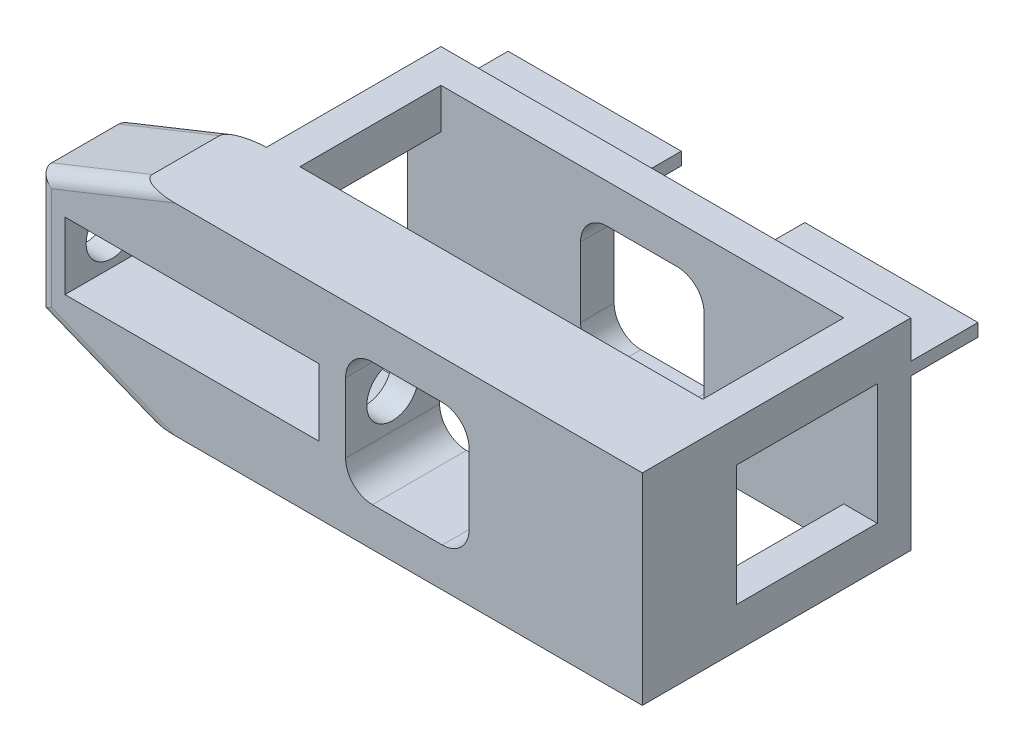
SolidWorks part; units mm, degrees
other "Markup1"
sketch "Sketch12" plane through (0, 38.1, 0) normal (-0.0705, 0.1614, 0.9844) x (0.9933, -0.0793, 0.0841)
material "ABS"
ref_plane "Front Plane" through (0, 0, 0) normal (0, 0, 1) x (1, 0, 0)
ref_plane "Top Plane" through (0, 0, 0) normal (0, 1, 0) x (1, 0, 0)
ref_plane "Right Plane" through (0, 0, 0) normal (1, 0, 0) x (0, 0, -1)
sketch "Sketch1" plane through (0, 0, 0) normal (0, 0, 1) x (1, 0, 0)
  line L1 (0, 0) -> (88.9, 0)
  line L2 (0, 0) -> (0, 38.1)
  line L3 (0, 38.1) -> (88.9, 38.1)
  line L4 (88.9, 0) -> (88.9, 38.1)
  line L5 (0, 0) -> (-25.4, 0)
  line L6 (0, 0) -> (0, 38.1)
  line L7 (0, 38.1) -> (-25.4, 38.1)
  line L8 (-25.4, 0) -> (-25.4, 38.1)
  dimension "D1" = 88.9
  dimension "D2" = 38.1
extrude "Boss-Extrude1" add sketch "Sketch1" against normal blind 17.78 contours L1 L4 L3 L2 | L8 L5 L2 L7 region at (44.45, 19.05, 0) region at (-12.7, 19.05, 0)
sketch "Sketch2" plane through (0, 0, 0) normal (0, 0, 1) x (1, 0, 0)
  line L0 (0, 19.05) -> (88.9, 19.05) construction
  line L1 (0, 0) -> (0, 38.1) construction
  line L2 (88.9, 0) -> (88.9, 38.1) construction
  line L3 (44.45, 0) -> (44.45, 38.1) construction
  line L4 (0, 0) -> (88.9, 0) construction
  line L5 (0, 38.1) -> (88.9, 38.1) construction
  line L6 (88.9, 30.48) -> (82.55, 30.48)
  line L7 (37.846, 30.734) -> (51.054, 30.734)
  line L8 (32.766, 25.654) -> (32.766, 12.446)
  line L9 (37.846, 7.366) -> (51.054, 7.366)
  line L10 (56.134, 25.654) -> (56.134, 12.446)
  line L11 (0, 38.1) -> (6.35, 38.1)
  line L12 (0, 38.1) -> (0, 30.48)
  line L13 (0, 30.48) -> (6.35, 30.48)
  line L14 (6.35, 38.1) -> (6.35, 30.48)
  line L15 (82.55, 38.1) -> (82.55, 30.48)
  line L16 (88.9, 38.1) -> (82.55, 38.1)
  line L17 (88.9, 38.1) -> (88.9, 30.48)
  line L18 (88.9, 0) -> (88.9, 7.62)
  line L19 (88.9, 0) -> (82.55, 0)
  line L20 (82.55, 0) -> (82.55, 7.62)
  line L21 (88.9, 7.62) -> (82.55, 7.62)
  line L22 (0, 7.62) -> (6.35, 7.62)
  line L23 (6.35, 0) -> (6.35, 7.62)
  line L24 (0, 0) -> (6.35, 0)
  line L25 (0, 0) -> (0, 7.62)
  line L26 (-25.4, 0) -> (-25.4, 38.1) construction
  line L27 (27.686, 25.4) -> (-10.414, 25.4)
  line L28 (27.686, 25.4) -> (27.686, 12.7)
  line L29 (27.686, 12.7) -> (-10.414, 12.7)
  line L30 (-10.414, 25.4) -> (-10.414, 12.7)
  line L31 (-25.4, 38.1) -> (88.9, 38.1) construction
  line L32 (-10.414, 25.4) -> (-20.32, 25.4)
  line L33 (-10.414, 25.4) -> (-10.414, 12.7)
  line L34 (-10.414, 12.7) -> (-20.32, 12.7)
  line L35 (-20.32, 25.4) -> (-20.32, 12.7)
  arc A0 (32.766, 12.446) -> (37.846, 7.366) centre (37.846, 12.446) ccw
  arc A1 (51.054, 7.366) -> (56.134, 12.446) centre (51.054, 12.446) ccw
  arc A2 (51.054, 30.734) -> (56.134, 25.654) centre (51.054, 25.654) cw
  arc A3 (37.846, 30.734) -> (32.766, 25.654) centre (37.846, 25.654) ccw
  point P47 (56.134, 7.366)
  point P50 (56.134, 30.734)
  point P53 (32.766, 30.734)
  dimension "D12" = 5.08
  dimension "D1" = 23.368
  dimension "D3" = 32.766
  dimension "D7" = 6.35
  dimension "D10" = 12.7
  dimension "D2" = 23.368
  dimension "D4" = 11.684
  dimension "D11" = 6.35
  dimension "D8" = 5.08
  dimension "D9" = 38.1
  dimension "D5" = 7.62
  dimension "D6" = 5.08
extrude "Cut-Extrude1" cut sketch "Sketch2" against normal blind 41.402 contours L27 L30 L29 L28 | L14 L11 L12 L13 | L25 L24 L23 L22 | L10 L7 L8 L9 | L17 L16 L15 L6 | L18 L21 L20 L19 | L33 L32 L35 L34 region at (85.725, 34.29, 0) region at (44.45, 19.05, 0) region at (3.175, 34.29, 0) region at (85.725, 3.81, 0) region at (3.175, 3.81, 0) region at (8.636, 19.05, 0)
ref_plane "Plane1" through (0, 0, -50.8) normal (0, 0, 1) x (1, 0, 0)
sketch "Sketch3" plane through (0, 0, -50.8) normal (0, 0, 1) x (1, 0, 0)
  line L0 (37.846, 30.734) -> (51.054, 30.734) construction
  line L3 (32.766, 25.654) -> (32.766, 12.446) construction
  line L4 (37.846, 7.366) -> (51.054, 7.366)
  line L5 (56.134, 12.446) -> (56.134, 25.654)
  line L6 (51.054, 30.734) -> (37.846, 30.734)
  line L7 (32.766, 25.654) -> (32.766, 12.446)
  line L8 (0, 0) -> (0, 38.1)
  line L94 (88.9, 30.48) -> (82.55, 30.48)
  line L96 (88.9, 7.62) -> (88.9, 30.48)
  line L98 (82.55, 7.62) -> (88.9, 7.62)
  line L104 (82.55, 0) -> (82.55, 7.62)
  line L105 (6.35, 0) -> (82.55, 0)
  line L106 (6.35, 7.62) -> (6.35, 0)
  line L107 (0, 7.62) -> (6.35, 7.62)
  line L108 (0, 0) -> (0, 7.62)
  line L109 (-25.4, 0) -> (0, 0)
  line L110 (-25.4, 38.1) -> (-25.4, 0)
  line L111 (0, 38.1) -> (-25.4, 38.1)
  line L112 (0, 30.48) -> (0, 38.1)
  line L113 (6.35, 30.48) -> (0, 30.48)
  line L114 (6.35, 38.1) -> (6.35, 30.48)
  line L115 (82.55, 38.1) -> (6.35, 38.1)
  line L116 (82.55, 30.48) -> (82.55, 38.1)
  line L117 (88.9, 30.48) -> (82.55, 30.48)
  line L118 (88.9, 7.62) -> (88.9, 30.48)
  line L119 (82.55, 7.62) -> (88.9, 7.62)
  line L120 (82.55, 0) -> (82.55, 7.62)
  line L121 (6.35, 0) -> (82.55, 0)
  line L122 (6.35, 7.62) -> (6.35, 0)
  line L123 (0, 7.62) -> (6.35, 7.62)
  line L124 (0, 0) -> (0, 7.62)
  line L125 (-25.4, 0) -> (0, 0)
  line L126 (-25.4, 38.1) -> (-25.4, 0)
  line L127 (0, 38.1) -> (-25.4, 38.1)
  line L128 (0, 30.48) -> (0, 38.1)
  line L129 (6.35, 30.48) -> (0, 30.48)
  line L130 (6.35, 38.1) -> (6.35, 30.48)
  line L131 (82.55, 38.1) -> (6.35, 38.1)
  line L132 (82.55, 30.48) -> (82.55, 38.1)
  arc A0 (37.846, 7.366) -> (32.766, 12.446) centre (37.846, 12.446) cw
  arc A1 (51.054, 7.366) -> (56.134, 12.446) centre (51.054, 12.446) ccw
  arc A2 (56.134, 25.654) -> (51.054, 30.734) centre (51.054, 25.654) ccw
  arc A3 (37.846, 30.734) -> (32.766, 25.654) centre (37.846, 25.654) ccw
  point P9 (32.766, 7.366)
  point P20 (56.134, 30.734)
  point P26 (32.766, 30.734)
  point P35 (32.766, 19.05)
  dimension "D5" = 5.08
  dimension "D2" = 0
  dimension "D4" = 23.368
  dimension "D6" = 23.368
  dimension "D8" = 0
  dimension "D1" = 0
extrude "Boss-Extrude2" add sketch "Sketch3" along normal blind 6.35 contours L117 L132 L131 L130 L129 L8 L123 L122 L121 L120 L119 L118 L7 L6 L5 L4 region at (0.9672, 19.05, -50.8)
sketch "Sketch6" plane through (-25.4, 0, 0) normal (-1, 0, 0) x (0, 0, 1)
  line L5 (-17.78, 25.4) -> (-17.78, 12.7)
  line L6 (-17.78, 12.7) -> (0, 12.7)
  line L7 (-17.78, 25.4) -> (-17.78, 12.7)
  line L8 (0, 25.4) -> (-17.78, 25.4)
  line L9 (0, 12.7) -> (0, 25.4)
  line L10 (-17.78, 12.7) -> (0, 12.7)
  line L12 (0, 25.4) -> (-17.78, 25.4)
  line L14 (0, 12.7) -> (0, 25.4)
  circle A0 centre (-8.89, 19.05) radius 4.8895
  dimension "D2" = 9.779
  dimension "D5" = 12.7
  dimension "D3" = 6.35
  dimension "D1" = 8.89
extrude "SpringPlunger Hole" cut sketch "Sketch6" against normal blind 89.916 contours A0
sketch "Sketch8" plane through (0, 0, 0) normal (0, 0, 1) x (1, 0, 0)
  line L30 (0, 0) -> (0, 38.1) construction
  line L31 (0, 38.1) -> (6.35, 38.1)
  line L32 (0, 38.1) -> (0, 30.1625)
  line L33 (0, 30.1625) -> (6.35, 30.1625)
  line L34 (6.35, 38.1) -> (6.35, 30.1625)
  line L35 (82.55, 38.1) -> (88.9, 38.1)
  line L36 (82.55, 38.1) -> (82.55, 30.1625)
  line L37 (82.55, 30.1625) -> (88.9, 30.1625)
  line L38 (88.9, 38.1) -> (88.9, 30.1625)
  line L39 (82.55, 7.9375) -> (88.9, 7.9375)
  line L40 (82.55, 7.9375) -> (82.55, 0)
  line L41 (82.55, 0) -> (88.9, 0)
  line L42 (88.9, 7.9375) -> (88.9, 0)
  line L43 (0, 7.9375) -> (6.35, 7.9375)
  line L44 (0, 7.9375) -> (0, 0)
  line L45 (0, 0) -> (6.35, 0)
  line L46 (6.35, 7.9375) -> (6.35, 0)
  line L48 (0, 0) -> (88.9, 0) construction
extrude "Support" add sketch "Sketch8" against normal up to surface (50.8 mm away) up to face at (44.45, 19.05, -50.8)
sketch "Sketch9" plane through (27.686, 0, 0) normal (-1, 0, 0) x (0, 0, 1)
  circle A3 centre (-8.89, 19.05) radius 4.8895
  dimension "D2" = 9.779
extrude "Cut-Extrude4" [suppressed] cut sketch "Sketch9" against normal up to surface (5.08 mm away) up to face at (32.766, 14.1605, -8.89)
sketch "Sketch10" plane through (0, 0, -50.8) normal (0, 0, -1) x (-1, 0, 0)
  line L1 (-88.9, 30.988) -> (0, 30.988)
  line L2 (-88.9, 30.988) -> (-88.9, 28.575)
  line L3 (-88.9, 28.575) -> (0, 28.575)
  line L4 (0, 30.988) -> (0, 28.575)
  line L8 (-88.9, 38.1) -> (0, 38.1) construction
  line L10 (-88.9, 0) -> (-88.9, 38.1) construction
  dimension "D1" = 7.112
  dimension "D2" = 88.9
  dimension "D3" = 2.413
extrude "Boss-Extrude3" add sketch "Sketch10" along normal blind 12.7
sketch "Sketch11" [suppressed] plane through (0, 0, 0) normal (0, 0, 1) x (1, 0, 0)
  line L0 (88.9, 0) -> (88.9, 38.1) construction
  line L1 (60.325, 27.94) -> (82.55, 27.94)
  line L2 (60.325, 27.94) -> (60.325, 6.35)
  line L3 (60.325, 6.35) -> (82.55, 6.35)
  line L4 (82.55, 27.94) -> (82.55, 6.35)
  line L5 (53.975, 28.575) -> (53.975, 9.525) construction
  line L6 (0, 38.1) -> (88.9, 38.1) construction
  line L7 (0, 0) -> (88.9, 0) construction
  dimension "D1" = 6.35
  dimension "D2" = 6.35
  dimension "D3" = 10.16
  dimension "D4" = 6.35
sketch "Sketch13" plane through (0, 0, 0) normal (0, 0, 1) x (1, 0, 0)
  line L0 (-6.35, 38.1) -> (-25.4, 30.48)
  line L1 (-25.4, 0) -> (-25.4, 38.1) construction
  line L2 (-6.35, 38.1) -> (-25.4, 38.1)
  line L3 (-25.4, 38.1) -> (-25.4, 30.48)
  line L4 (-6.35, 0) -> (-25.4, 0)
  line L5 (-25.4, 0) -> (-25.4, 7.62)
  line L6 (-25.4, 7.62) -> (-6.35, 0)
  line L7 (-25.4, 0) -> (88.9, 0) construction
  line M4 (88.9, 38.1) -> (-25.4, 38.1)
  line M5 (-25.4, 38.1) -> (-25.4, 0)
  line M6 (-25.4, 0) -> (88.9, 0)
  dimension "D1" = 7.62
  dimension "D2" = 7.62
  dimension "D3" = 6.35
  dimension "D4" = 6.35
extrude "Cut-Extrude5" cut sketch "Sketch13" against normal up to surface (17.78 mm away) contours L0 M4 M5 | L6 M5 M6 region at (-19.05, 2.54, 0) region at (-19.05, 35.56, 0) up to face at (44.45, 19.05, -17.78)
fillet "Fillet1" radius 2.54 6 edges at (-15.875, 3.81, 0) (-15.875, 3.81, -17.78) (-15.875, 34.29, -17.78) (-15.875, 34.29, 0) (-25.4, 19.05, 0) (-25.4, 19.05, -17.78)
sketch "Sketch14" plane through (0, 30.988, 0) normal (0, 1, 0) x (1, 0, 0)
  line L0 (88.9, 50.8) -> (0, 50.8) construction
  line L1 (32.766, 50.8) -> (56.134, 50.8)
  line L2 (32.766, 50.8) -> (32.766, 63.5)
  line L3 (32.766, 63.5) -> (56.134, 63.5)
  line L4 (56.134, 50.8) -> (56.134, 63.5)
  line L5 (0, 63.5) -> (88.9, 63.5) construction
  line L6 (0, 63.5) -> (0, 50.8) construction
  dimension "D1" = 23.368
  dimension "D2" = 32.766
extrude "Cut-Extrude6" cut sketch "Sketch14" against normal up to next
equation "\"box\"= 3.5"
equation "\"D1@Sketch1\"=\"box\""
equation "\"shaft\"=0.92"
equation "\"D1@Sketch2\"=\"shaft\""
equation "\"D3@Sketch2\"=(\"box\"-\"shaft\")/2"
equation "\"D7@Sketch2\"=0.25"
equation "\"springHole\"=1"
equation "\"depth1\"=0.7"
equation "\"D1@Boss-Extrude1\"=\"depth1\""
equation "\"springShaftD\"=0.385"
equation "\"D2@Sketch6\"=\"springShaftD\""
equation "\"D2@Sketch1\"=(\"box\"/3.5)*1.5"
equation "\"D2@Sketch2\"=\"shaft\""
equation "\"D4@Sketch2\"=\"shaft\"/2"
equation "\"D11@Sketch2\"=\"D10@Sketch2\"/2"
equation "\"D3@Sketch6\"=\"D5@Sketch6\"/2"
equation "\"springPinD\"=0.385"
equation "\"D2@Sketch9\"=\"springPinD\""
